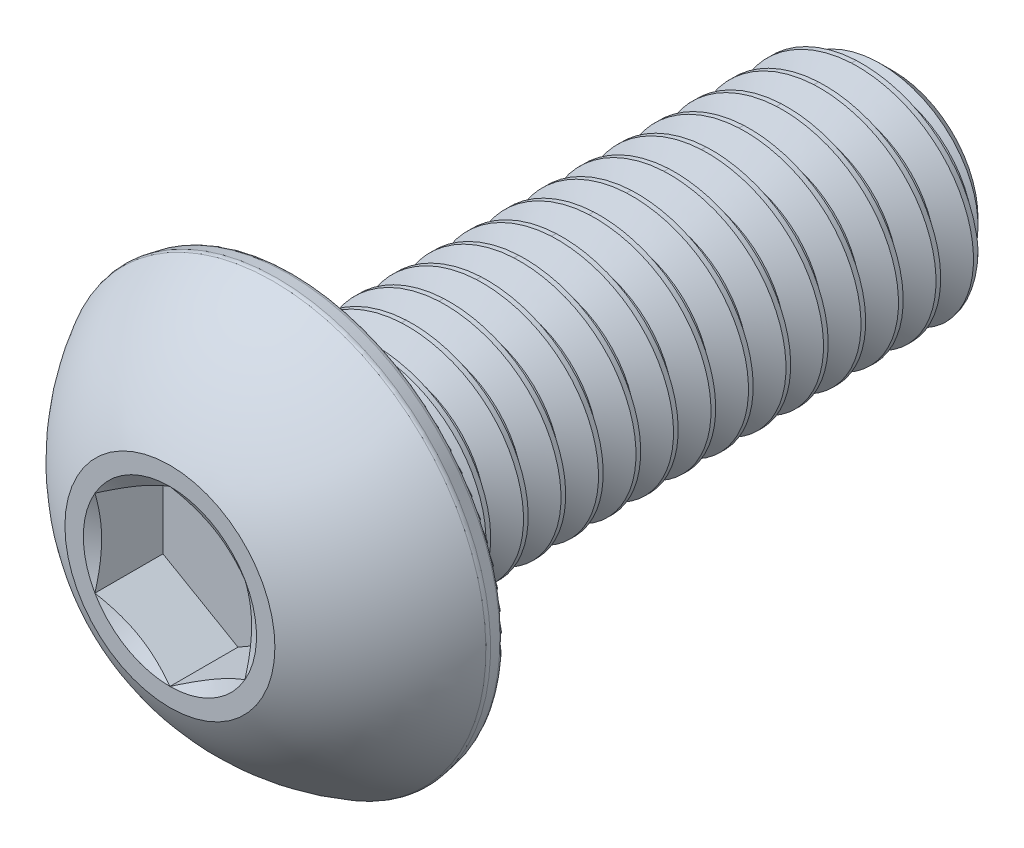
SolidWorks part; units mm, degrees
ref_plane "Front Plane" through (0, 0, 0) normal (0, 0, 1) x (1, 0, 0)
ref_plane "Top Plane" through (0, 0, 0) normal (0, 1, 0) x (1, 0, 0)
ref_plane "Right Plane" through (0, 0, 0) normal (1, 0, 0) x (0, 0, -1)
sketch "Sketch1" plane through (0, 0, 0) normal (1, 0, 0) x (0, 0, -1)
  line L0 (0, 0) -> (8, 0) construction
  line L1 (8, 1.5) -> (8, -1.5) construction
  line L2 (0, 0) -> (-1.65, 0) construction
  line L3 (0, 2.85) -> (0, -2.85) construction
  line L4 (-1.65, 1) -> (-1.65, -1) construction
  line L5 (7.9687, 1.5541) -> (8.4687, 1.5541) construction
  line L6 (8.4687, 1.5541) -> (8.2187, 1.1211) construction
  line L7 (8.2187, 1.1211) -> (7.9687, 1.5541) construction
  line L8 (7.9844, 1.5271) -> (8.4531, 1.5271) construction
  line L9 (8, 1.5) -> (8.4375, 1.5) construction
  line L10 (8.1875, 1.1752) -> (8.25, 1.1752) construction
  line L11 (8.2187, 1.1752) -> (8.2187, 1.1211) construction
  line L12 (8.2187, 1.5) -> (8.2187, 1.5541) construction
  point P5 (8, 0)
  point P10 (-1.65, 0)
  point P13 (0, 0)
  point P18 (6.75, -1.5)
  point P25 (8.2187, 1.5271)
  dimension "Thread Size" = 3
  dimension "Length" = 8
  dimension "Head Diameter" = 5.7
  dimension "Drive Size" = 2
  dimension "Head Height" = 1.65
  dimension "D1" = 60
  dimension "Thread Pitch" = 0.5
  dimension "D2" = 0.0625
  dimension "D3" = 1.25
sketch "Sketch2" plane through (0, 0, 0) normal (1, 0, 0) x (0, 0, -1)
  line L0 (8, 0) -> (-1.65, 0)
  line L1 (-1.65, 0) -> (-1.65, 1.4)
  line L2 (-1.65, 0) -> (-1.65, 2.85) construction
  line L3 (-1.65, 2.85) -> (0, 2.85) construction
  line L4 (0, 2.8064) -> (-0.2475, 2.85)
  line L5 (0, 2.85) -> (0, -2.85) construction
  line L6 (0, 2.8064) -> (0, 1.5)
  line L7 (0, 1.5) -> (7.625, 1.5)
  line L8 (7.625, 1.5) -> (8, 1.125)
  line L9 (8, 1.5) -> (8, -1.5) construction
  line L10 (8, 1.125) -> (8, 0)
  line L11 (-1.65, 0) -> (-1.65, -1.4) construction
  arc A0 (-0.2475, 2.85) -> (-1.65, 1.4) centre (1.2482, 0) ccw
  dimension "D1" = 45
  dimension "D2" = 0.375
  dimension "D3" = 10
  dimension "D4" = 0.2475
  dimension "D5" = 2.8
revolve "Revolve1" add sketch "Sketch2" angle 360 about L0
sketch "Sketch3" plane through (0, 0, 1.65) normal (0, 0, 1) x (1, 0, 0)
  line L1 (0, 1.1547) -> (-1, 0.5774)
  line L2 (-1, 0.5774) -> (-1, -0.5774)
  line L3 (-1, -0.5774) -> (0, -1.1547)
  line L4 (0, -1.1547) -> (1, -0.5774)
  line L5 (1, -0.5774) -> (1, 0.5774)
  line L6 (1, 0.5774) -> (0, 1.1547)
  circle A0 centre (0, 0) radius 1 construction
extrude "Cut-Extrude1" cut sketch "Sketch3" against normal blind 0.9075
sketch "Sketch4" plane through (0, 0, 1.65) normal (0, 0, 1) x (1, 0, 0)
  circle A0 centre (0, 0) radius 1.1547
extrude "Cut-Extrude2" cut sketch "Sketch4" against normal blind 0.9075 draft 60
fillet "Fillet1" radius 0.0825 2 edges at (0, 2.85, 0.2475) (0, 2.8064, 0)
sketch "Sketch8" plane through (0, 0, 0) normal (0, 0, 1) x (1, 0, 0)
  circle A0 centre (0, 0) radius 2.85 construction
  circle A1 centre (0, 0) radius 1 construction
ref_plane "Plane1" through (0, 0, -0.225) normal (0, 0, 1) x (1, 0, 0)
split "Split1" trim tools "Plane1" bodies to split 106 resulting bodies 107 108
sketch "Sketch5" plane through (0, 0, 0) normal (1, 0, 0) x (0, 0, -1)
  line L0 (7.9844, 1.5271) -> (8.4531, 1.5271)
  line L1 (8.4531, 1.5271) -> (8.25, 1.1752)
  line L2 (8.25, 1.1752) -> (8.1875, 1.1752)
  line L3 (8.1875, 1.1752) -> (7.9844, 1.5271)
sketch "Sketch6" plane through (0, 0, -8) normal (0, 0, -1) x (-1, 0, 0)
  circle A0 centre (0, 0) radius 1.5
curve "Helix/Spiral1" pitch 0.5 height 8.5 radius 1.5 centre (0, 0, -8) axis (0, 0, 1) start towards (0, 1, 0)
sweep "Cut-Sweep1" cut profiles "Sketch5" path "Helix/Spiral1" align with end faces yes
combine bodies "Combine1" operation type add bodies to combine 109 107
sketch "Sketch7" plane through (0, 0, -0.225) normal (0, 0, 1) x (1, 0, 0)
  circle A0 centre (0, 0) radius 1.5
extrude "Boss-Extrude1" add sketch "Sketch7" against normal blind 1.25 draft 45
fillet "Fillet2" radius 0.0825 1 edges at (0, 1.5, 0)
equation "\"D2@Sketch1\"=\"Thread Pitch@Sketch1\"/8"
equation "\"D2@Sketch2\"=\"Thread Pitch@Sketch1\"*.75"
equation "\"D4@Sketch2\"=\"Head Height@Sketch1\"*.15"
equation "\"D5@Sketch2\"=\"Drive Size@Sketch1\"*1.4"
equation "\"D1@Cut-Extrude1\"=\"Head Height@Sketch1\"*.55"
equation "\"D1@Cut-Extrude2\"=\"D1@Cut-Extrude1\""
equation "\"D1@Fillet1\"=\"Head Height@Sketch1\"*.05"
equation "\"D4@Helix/Spiral1\"=\"Thread Pitch@Sketch1\""
equation "\"D3@Helix/Spiral1\"=\"Length@Sketch1\"+\"Thread Pitch@Sketch1\""
equation "\"D3@Sketch1\"=\"Thread Pitch@Sketch1\"*2.5"
equation "\"D1@Fillet2\"=\"D1@Fillet1\""
equation "\"D1@Plane1\"=\"Thread Pitch@Sketch1\"*.45"
equation "\"D1@Boss-Extrude1\"=\"Thread Pitch@Sketch1\"*2.5"
